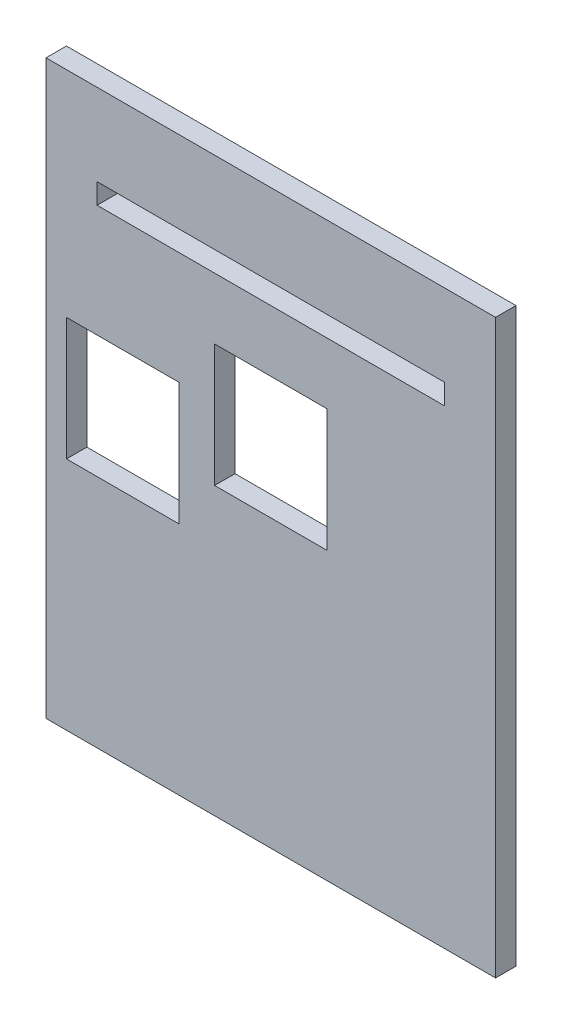
SolidWorks part; units mm, degrees
ref_plane "Front" through (0, 0, 0) normal (0, 0, 1) x (1, 0, 0)
ref_plane "Top" through (0, 0, 0) normal (0, 1, 0) x (1, 0, 0)
ref_plane "Right" through (0, 0, 0) normal (1, 0, 0) x (0, 0, -1)
sketch "Esquisse1" plane through (0, 0, 0) normal (0, 0, 1) x (1, 0, 0)
  line L1 (0, 0) -> (220, 0)
  line L2 (0, 0) -> (0, 280)
  line L3 (0, 280) -> (220, 280)
  line L4 (220, 0) -> (220, 280)
  dimension "D1" = 220
  dimension "D2" = 280
extrude "Boss.-Extru.1" add sketch "Esquisse1" along normal blind 10
sketch "Esquisse2" plane through (0, 0, 0) normal (0, -1, 0) x (1, 0, 0)
  line L0 (0, 5) -> (220, 5) construction
  line L1 (0, 10) -> (0, 0) construction
  line L2 (220, 10) -> (220, 0) construction
  line L3 (110, 5) -> (110, 28.0559) construction
  circle A0 centre (110, 5) radius 2
  circle A1 centre (210, 5) radius 2
  circle A2 centre (10, 5) radius 2
  dimension "D1" = 4
  dimension "D2" = 100
extrude "Enlèv. mat.-Extru.1" cut sketch "Esquisse2" against normal blind 10
sketch "Esquisse3" plane through (0, 0, 10) normal (0, 0, 1) x (1, 0, 0)
  line L0 (110, 0) -> (110, 280) construction
  line L1 (0, 0) -> (220, 0) construction
  line L2 (220, 280) -> (0, 280) construction
  line L3 (82.5, 200) -> (137.5, 200)
  line L4 (137.5, 200) -> (137.5, 140)
  line L5 (137.5, 140) -> (82.5, 140)
  line L6 (82.5, 200) -> (82.5, 140)
  line L8 (10, 175) -> (65, 175)
  line L9 (10, 175) -> (10, 115)
  line L10 (10, 115) -> (65, 115)
  line L11 (65, 175) -> (65, 115)
  point P11 (110, 140)
  point P12 (110, 200)
  dimension "D1" = 60
  dimension "D2" = 55
  dimension "D3" = 140
  dimension "D4" = 55
  dimension "D5" = 45
  dimension "D6" = 60
  dimension "D7" = 115
extrude "Enlèv. mat.-Extru.2" cut sketch "Esquisse3" against normal through all both and the other way through all
sketch "Esquisse5" plane through (0, 0, 10) normal (0, 0, 1) x (1, 0, 0)
  line L0 (110, 230) -> (110, 0) construction
  line L1 (25, 240) -> (195, 240)
  line L2 (25, 240) -> (25, 230)
  line L3 (25, 230) -> (195, 230)
  line L4 (195, 240) -> (195, 230)
  line L5 (0, 0) -> (220, 0) construction
  dimension "D1" = 170
  dimension "D2" = 10
  dimension "D3" = 230
extrude "Enlèv. mat.-Extru.3" cut sketch "Esquisse5" against normal through all both and the other way through all
